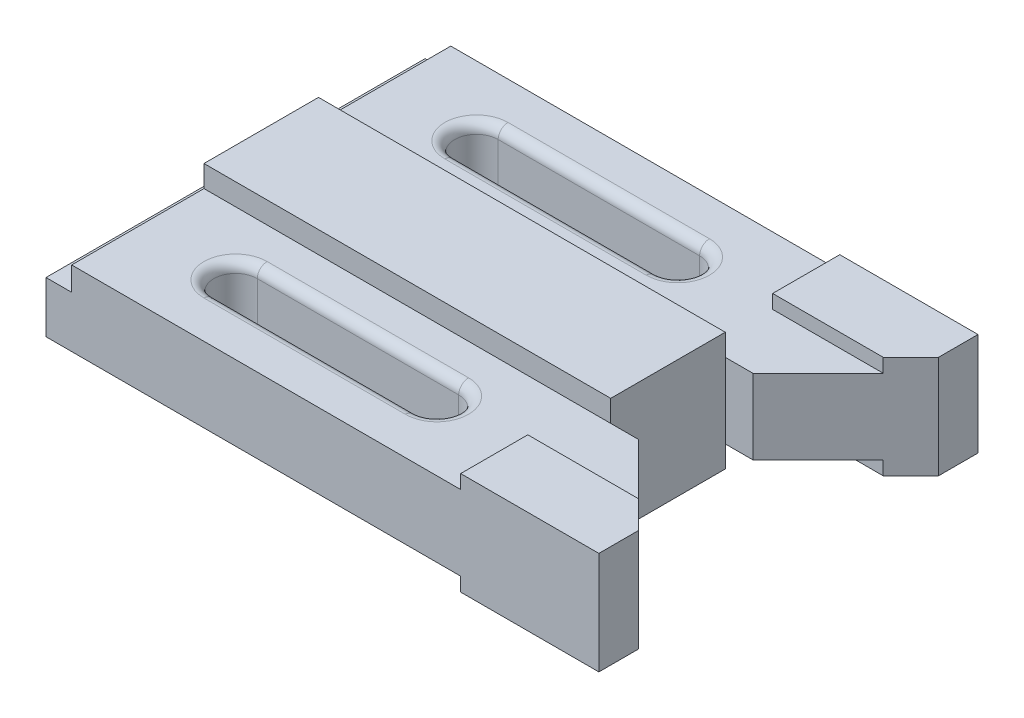
SolidWorks part; units mm, degrees
material "1060 Alloy"
ref_plane "Front Plane" through (0, 0, 0) normal (0, 0, 1) x (1, 0, 0)
ref_plane "Top Plane" through (0, 0, 0) normal (0, 1, 0) x (1, 0, 0)
ref_plane "Right Plane" through (0, 0, 0) normal (1, 0, 0) x (0, 0, -1)
sketch "Sketch1" plane through (0, 0, 0) normal (0, 1, 0) x (1, 0, 0)
  line L0 (0, 0) -> (140, 0)
  line L1 (0, 0) -> (0, -48)
  line L2 (0, -48) -> (109.5, -48)
  line L3 (109.5, -48) -> (109.5, -33.5)
  line L4 (109.5, -33.5) -> (116.5, -33.5)
  line L5 (116.5, -33.5) -> (140, -10)
  line L6 (140, -10) -> (140, 0)
  line L7 (105, 0) -> (105, -17)
  line L8 (105, -17) -> (133, -17)
  line L9 (30.5, -17.5) -> (81.5, -17.5) construction
  line L10 (30.5, -12) -> (81.5, -12)
  line L11 (30.5, -23) -> (81.5, -23)
  line L12 (109.5, -33.5) -> (0, -33.5)
  arc A0 (30.5, -12) -> (30.5, -23) centre (30.5, -17.5) ccw
  arc A1 (81.5, -23) -> (81.5, -12) centre (81.5, -17.5) ccw
  point P13 (56, -17.5)
  dimension "D12" = 5.5
  dimension "D1" = 140
  dimension "D2" = 48
  dimension "D3" = 10
  dimension "D4" = 33.5
  dimension "D5" = 35
  dimension "D6" = 17
  dimension "D7" = 45
  dimension "D8" = 30.5
  dimension "D9" = 30.5
  dimension "D10" = 17.5
  dimension "D11" = 51
extrude "Boss-Extrude5" add sketch "Sketch1" along normal mid plane 30 contours L3 L12 L1 L2 region at (54.75, 0, 40.75)
extrude "Boss-Extrude6" add sketch "Sketch1<3>" along normal mid plane 19 contours L12 L4 L5 L8 L7 L0 L1 A1 L11 A0 L10 region at (52.5, 0, 1.3715)
sketch "Sketch1<3>" plane through (0, 0, 0) normal (0, 1, 0) x (1, 0, 0) same geometry as "Sketch1"
extrude "Boss-Extrude8" add sketch "Sketch1<5>" along normal mid plane 26 contours L7 L8 L5 L6 L0 region at (121.8487, 0, 8.2352)
sketch "Sketch1<5>" plane through (0, 0, 0) normal (0, 1, 0) x (1, 0, 0) same geometry as "Sketch1"
sketch "Sketch4" plane through (0, 0, 0) normal (0, 0, -1) x (-1, 0, 0)
  line L1 (0, 15) -> (-6.5, 15)
  line L2 (0, 15) -> (0, 3.5)
  line L3 (0, 3.5) -> (-6.5, 3.5)
  line L4 (-6.5, 15) -> (-6.5, 3.5)
  dimension "D1" = 11.5
  dimension "D2" = 6.5
extrude "Cut-Extrude3" cut sketch "Sketch4" against normal mid plane 131
fillet "Fillet2" radius 2.5 8 edges at (87, -9.5, 17.5) (56, -9.5, 12) (25, -9.5, 17.5) (56, -9.5, 23) (25, 9.5, 17.5) (56, 9.5, 23) (56, 9.5, 12) (87, 9.5, 17.5)
mirror "Mirror2" about plane through (0, 15, 48) normal (0, 0, -1) of bodies 112
equation "\"a\"= 140mm"
equation "\"b\"= 51mm"
equation "\"c\"= 45deg"
